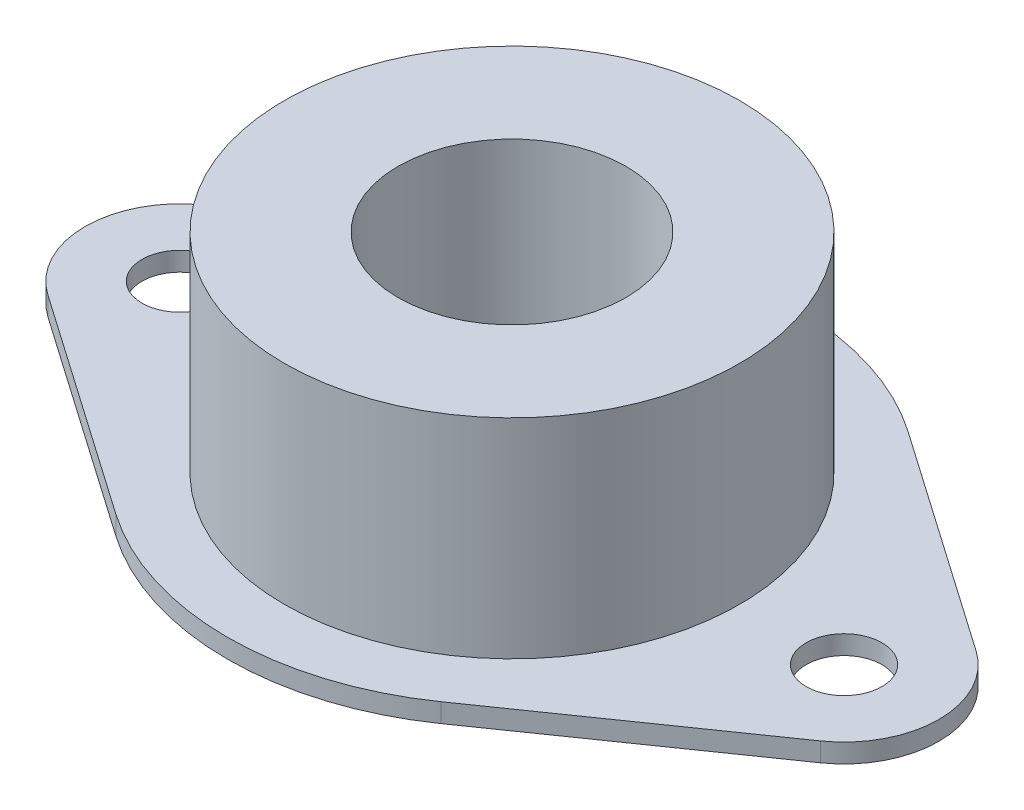
SolidWorks part; units mm, degrees
ref_plane "前视基准面" through (0, 0, 0) normal (0, 0, 1) x (1, 0, 0)
ref_plane "上视基准面" through (0, 0, 0) normal (0, 1, 0) x (1, 0, 0)
ref_plane "右视基准面" through (0, 0, 0) normal (1, 0, 0) x (0, 0, -1)
sketch "草图1" plane through (0, 0, 0) normal (0, 1, 0) x (1, 0, 0)
  line L0 (0, 16.1664) -> (0, -14.6805) construction
  line L1 (-18.4844, 0) -> (22.4368, 0) construction
  line L2 (-22.5, 0) -> (-22.5, 6.4487) construction
  line L3 (22.5, 0) -> (22.5, 7.162) construction
  line L4 (8.5714, 12.3098) -> (20.3571, 4.1033)
  line L5 (-8.5714, 12.3098) -> (-20.3571, 4.1033)
  line L6 (8.5714, -12.3098) -> (20.3571, -4.1033)
  line L7 (-8.5714, -12.3098) -> (-20.3571, -4.1033)
  circle A0 centre (0, 0) radius 6
  circle A1 centre (0, 0) radius 10.1305
  circle A3 centre (17.5, 0) radius 2
  circle A4 centre (-17.5, 0) radius 2
  circle A5 centre (-17.5, 0) radius 5
  circle A6 centre (17.5, 0) radius 5
  circle A7 centre (0, 0) radius 15
  circle A8 centre (0, 0) radius 12
  dimension "D2" = 4
  dimension "D3" = 30
  dimension "D5" = 24
  dimension "D6" = 12
  dimension "D1" = 35
  dimension "D4" = 45
extrude "凸台-拉伸1" add sketch "草图1" along normal blind 1 contours A7 A5 A4 | A7 A5 L7 | A7 L5 A5 | A6 A7 A5 A8 | A7 A6 L4 | A7 L6 A6 | A7 A6 A3 | A5 | A6 | A4 | A3 | A8 region at (11.9086, 0, -8.4176) region at (14.7945, 0, -6.7694) region at (21.8183, 0, -2.2552) region at (-14.7945, 0, -6.7694) region at (-17.3923, 0, -4.8705) region at (14.7945, 0, 6.7694) region at (-14.7945, 0, 6.7694)
extrude "凸台-拉伸2" add sketch "草图1<3>" along normal blind 12 contours A8 A1 | A1 A0 region at (-9.844, 0, 0) region at (-11.6606, 0, 0)
sketch "草图1<3>" plane through (0, 0, 0) normal (0, 1, 0) x (1, 0, 0) same geometry as "草图1"
